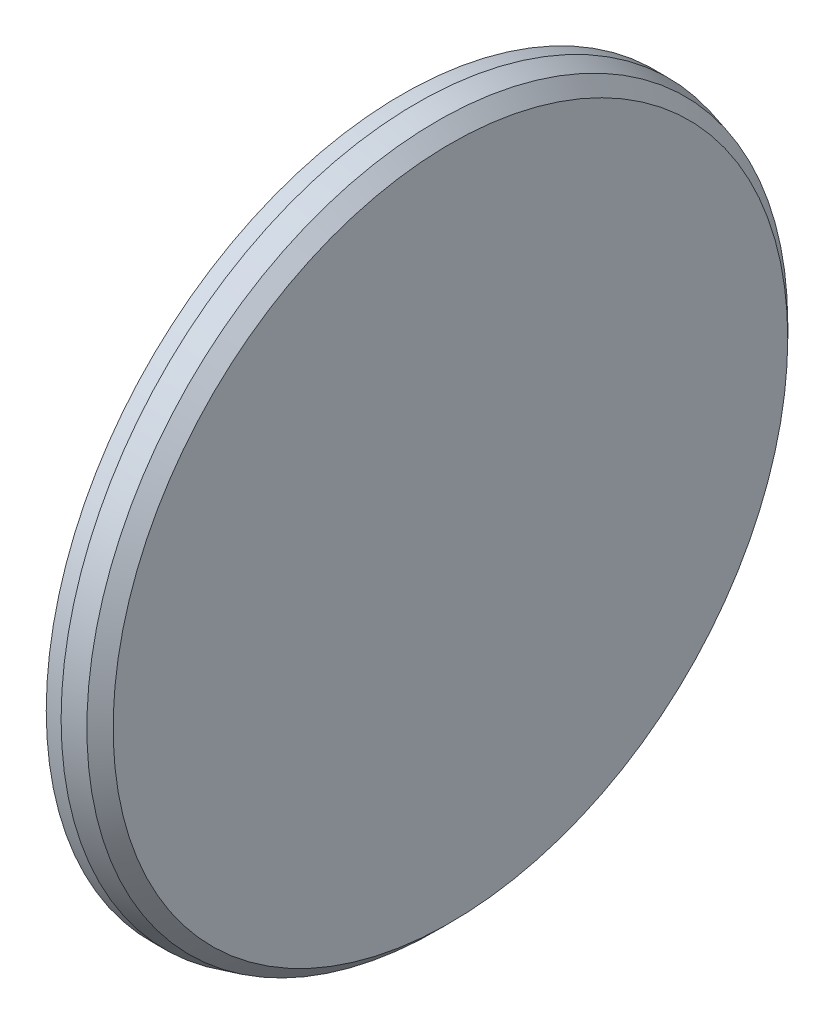
SolidWorks part; units mm, degrees
material "1060 Alloy"
ref_plane "Front Plane" through (0, 0, 0) normal (0, 0, 1) x (1, 0, 0)
ref_plane "Top Plane" through (0, 0, 0) normal (0, 1, 0) x (1, 0, 0)
ref_plane "Right Plane" through (0, 0, 0) normal (1, 0, 0) x (0, 0, -1)
sketch "Sketch1" plane through (0, 0, 0) normal (0, 1, 0) x (1, 0, 0)
  line L0 (0, 0) -> (-85, 0) construction
  line L1 (-85, 0) -> (-85, 100)
  line L2 (-85, 100) -> (-30, 100)
  line L3 (-30, 100) -> (-30, 433.75)
  line L4 (-30, 433.75) -> (-65, 433.75)
  line L5 (-65, 433.75) -> (-65, 478.75)
  line L6 (-65, 478.75) -> (-45, 478.75)
  line L7 (-45, 478.75) -> (-17.6795, 471.4295)
  line L8 (-17.6795, 471.4295) -> (0, 453.75)
  line L9 (0, 453.75) -> (0, 0)
  line L10 (0, 0) -> (-85, 0)
  point P10 (-55, 478.75)
  dimension "D1" = 100
  dimension "D2" = 20
  dimension "D3" = 45
  dimension "D4" = 15
  dimension "D5" = 45
  dimension "D6" = 30
  dimension "D7" = 65
  dimension "D8" = 85
  dimension "D9" = 478.75
  dimension "D10" = 453.75
revolve "Revolve1" add sketch "Sketch1" angle 360 about L0
sketch "Sketch2" plane through (-30, 0, 0) normal (-1, 0, 0) x (0, 0, 1)
  line L0 (0, 100) -> (0, 433.75) construction
  line L1 (20, 105.8301) -> (20, 422.6867)
  line L2 (-20, 105.8301) -> (-20, 365.0877)
  line L3 (-20, 100) -> (-20, 433.75) construction
  line L4 (20, 100) -> (20, 433.75) construction
  line L5 (83.3471, 68.2148) -> (287.0187, 310.9411)
  line L6 (52.7054, 93.9263) -> (219.353, 292.5292)
  line L7 (64.2788, 76.6044) -> (278.8091, 332.2718) construction
  line L8 (107.6952, -1.319) -> (419.7381, 53.7026)
  line L9 (100.7493, 38.0734) -> (356.0683, 83.093)
  line L10 (98.4808, 17.3648) -> (427.1604, 75.3199) construction
  line L11 (81.6515, -70.2355) -> (356.0574, -228.6639)
  line L12 (101.6515, -35.5945) -> (326.1753, -165.2234)
  line L13 (86.6025, -50) -> (375.6385, -216.875) construction
  line L14 (17.4022, -106.2881) -> (125.7735, -404.036)
  line L15 (54.9899, -92.6073) -> (143.6612, -336.2299)
  line L16 (34.202, -93.9693) -> (148.3512, -407.5917) construction
  line L17 (-54.9899, -92.6073) -> (-163.3612, -390.3552)
  line L18 (-17.4022, -106.2881) -> (-106.0735, -349.9107)
  line L19 (-34.202, -93.9693) -> (-148.3512, -407.5917) construction
  line L20 (-101.6515, -35.5945) -> (-376.0574, -194.0229)
  line L21 (-81.6515, -70.2355) -> (-306.1753, -199.8644)
  line L22 (-86.6025, -50) -> (-375.6385, -216.875) construction
  line L23 (-100.7493, 38.0734) -> (-412.7922, 93.0949)
  line L24 (-107.6952, -1.319) -> (-363.0142, 43.7007)
  line L25 (-98.4808, 17.3648) -> (-427.1604, 75.3199) construction
  line L26 (-52.7054, 93.9263) -> (-256.3769, 336.6526)
  line L27 (-83.3471, 68.2148) -> (-249.9948, 266.8177)
  line L28 (-64.2788, 76.6044) -> (-278.8091, 332.2718) construction
  circle A0 centre (0, 0) radius 100 construction
  circle A1 centre (0, 0) radius 433.75 construction
  arc A4 (20, 422.6867) -> (30.708, 432.6616) centre (30, 422.6867) cw
  arc A5 (287.0187, 310.9411) -> (301.6332, 311.6993) centre (294.6791, 304.5132) cw
  arc A6 (-20, 365.0877) -> (-92.8428, 423.6972) centre (-80, 365.0877) ccw
  arc A7 (20, 105.8301) -> (27.2727, 96.2091) centre (30, 105.8301) ccw
  arc A8 (-20, 105.8301) -> (-27.2727, 96.2091) centre (-30, 105.8301) cw
  arc A9 (219.353, 292.5292) -> (201.2256, 384.2491) centre (173.3903, 331.0964) ccw
  arc A10 (83.3471, 68.2148) -> (82.7342, 56.1699) centre (91.0076, 61.7869) ccw
  arc A11 (52.7054, 93.9263) -> (40.9499, 91.231) centre (45.0449, 100.3542) cw
  arc A12 (419.7381, 53.7026) -> (431.4209, 44.8895) centre (421.4746, 43.8545) cw
  arc A13 (356.0683, 83.093) -> (401.1383, 165.0066) centre (345.6494, 142.1814) ccw
  arc A14 (107.6952, -1.319) -> (99.4834, -10.1519) centre (109.4317, -11.167) ccw
  arc A15 (100.7493, 38.0734) -> (90.0116, 43.5649) centre (99.0128, 47.9214) cw
  arc A16 (356.0574, -228.6639) -> (359.342, -242.9247) centre (351.0574, -237.3241) cw
  arc A17 (326.1753, -165.2234) -> (413.3539, -131.4443) centre (356.1753, -113.2618) ccw
  arc A18 (81.6515, -70.2355) -> (69.6832, -71.7234) centre (76.6515, -78.8958) ccw
  arc A19 (101.6515, -35.5945) -> (96.9559, -24.4857) centre (106.6515, -26.9343) cw
  arc A20 (125.7735, -404.036) -> (119.1229, -417.0717) centre (116.3766, -407.4562) cw
  arc A21 (143.6612, -336.2299) -> (232.1567, -366.391) centre (200.0428, -315.7086) ccw
  arc A22 (17.4022, -106.2881) -> (7.2775, -99.7348) centre (8.0052, -109.7083) ccw
  arc A23 (54.9899, -92.6073) -> (58.5334, -81.0792) centre (64.3868, -89.1871) cw
  arc A24 (-163.3612, -390.3552) -> (-176.835, -396.0662) centre (-172.7582, -386.935) cw
  arc A25 (-106.0735, -349.9107) -> (-57.6693, -429.8992) centre (-49.692, -370.4319) ccw
  arc A26 (-54.9899, -92.6073) -> (-58.5334, -81.0792) centre (-64.3868, -89.1871) ccw
  arc A27 (-17.4022, -106.2881) -> (-7.2775, -99.7348) centre (-8.0052, -109.7083) cw
  arc A28 (-376.0574, -194.0229) -> (-390.0499, -189.7369) centre (-381.0574, -185.3626) cw
  arc A29 (-306.1753, -199.8644) -> (-320.5111, -292.2528) centre (-276.1753, -251.8259) ccw
  arc A30 (-101.6515, -35.5945) -> (-96.9559, -24.4857) centre (-106.6515, -26.9343) ccw
  arc A31 (-81.6515, -70.2355) -> (-69.6832, -71.7234) centre (-76.6515, -78.8958) cw
  arc A32 (-412.7922, 93.0949) -> (-420.7561, 105.3723) centre (-411.0557, 102.943) cw
  arc A33 (-363.0142, 43.7007) -> (-433.3822, -17.8581) centre (-373.4331, -15.3878) ccw
  arc A34 (-100.7493, 38.0734) -> (-90.0116, 43.5649) centre (-99.0128, 47.9214) ccw
  arc A35 (-107.6952, -1.319) -> (-99.4834, -10.1519) centre (-109.4317, -11.167) cw
  arc A36 (-256.3769, 336.6526) -> (-254.5859, 351.1767) centre (-248.7165, 343.0804) cw
  arc A37 (-249.9948, 266.8177) -> (-343.469, 264.8926) centre (-295.9574, 228.2504) ccw
  arc A38 (-52.7054, 93.9263) -> (-40.9499, 91.231) centre (-45.0449, 100.3542) ccw
  arc A39 (-83.3471, 68.2148) -> (-82.7342, 56.1699) centre (-91.0076, 61.7869) cw
  arc A40 (82.7342, 56.1699) -> (40.9499, 91.231) centre (0, 0) ccw
  arc A41 (-420.7561, 105.3723) -> (-433.3822, -17.8581) centre (0, 0) ccw
  arc A42 (-254.5859, 351.1767) -> (-343.469, 264.8926) centre (0, 0) ccw
  arc A43 (30.708, 432.6616) -> (-92.8428, 423.6972) centre (0, 0) ccw
  arc A44 (-390.0499, -189.7369) -> (-320.5111, -292.2528) centre (0, 0) ccw
  arc A45 (-176.835, -396.0662) -> (-57.6693, -429.8992) centre (0, 0) ccw
  arc A46 (119.1229, -417.0717) -> (232.1567, -366.391) centre (0, 0) ccw
  arc A47 (359.342, -242.9247) -> (413.3539, -131.4443) centre (0, 0) ccw
  arc A48 (431.4209, 44.8895) -> (401.1383, 165.0066) centre (0, 0) ccw
  arc A49 (301.6332, 311.6993) -> (201.2256, 384.2491) centre (0, 0) ccw
  arc A50 (99.4834, -10.1519) -> (90.0116, 43.5649) centre (0, 0) ccw
  arc A51 (27.2727, 96.2091) -> (-27.2727, 96.2091) centre (0, 0) ccw
  arc A52 (-40.9499, 91.231) -> (-82.7342, 56.1699) centre (0, 0) ccw
  arc A53 (-90.0116, 43.5649) -> (-99.4834, -10.1519) centre (0, 0) ccw
  arc A54 (-96.9559, -24.4857) -> (-69.6832, -71.7234) centre (0, 0) ccw
  arc A55 (-58.5334, -81.0792) -> (-7.2775, -99.7348) centre (0, 0) ccw
  arc A56 (7.2775, -99.7348) -> (58.5334, -81.0792) centre (0, 0) ccw
  arc A57 (69.6832, -71.7234) -> (96.9559, -24.4857) centre (0, 0) ccw
  circle A58 centre (0, 0) radius 433.75 construction
  point P13 (0, 0)
  point P139 (0, 0)
  dimension "D3" = 10
  dimension "D4" = 60
  dimension "D5" = 10
  dimension "D6" = 9
  dimension "D7" = 433.75
  dimension "D8" = 100
  dimension "D1" = 20
  dimension "D2" = 20
extrude "Boss-Extrude1" add sketch "Sketch2" along normal blind 25
